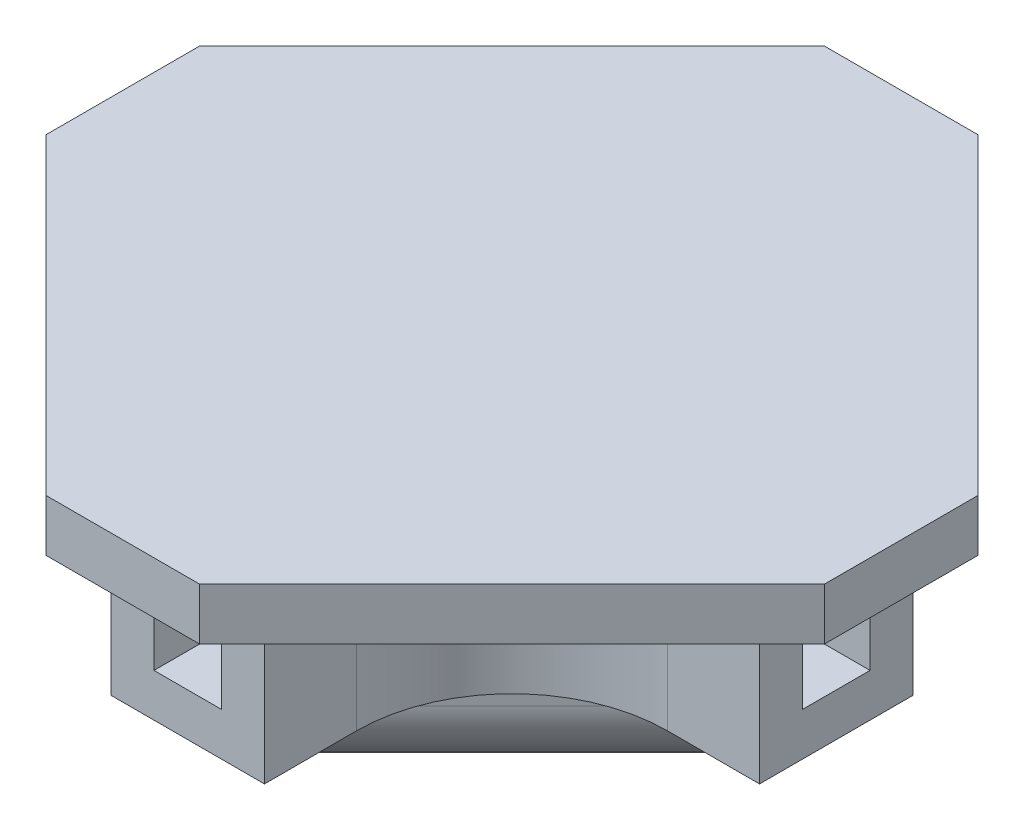
SolidWorks part; units mm, degrees
material "ABS"
ref_plane "Front Plane" through (0, 0, 0) normal (0, 0, 1) x (1, 0, 0)
ref_plane "Top Plane" through (0, 0, 0) normal (0, 1, 0) x (1, 0, 0)
ref_plane "Right Plane" through (0, 0, 0) normal (1, 0, 0) x (0, 0, -1)
sketch "Sketch1" plane through (0, 0, 0) normal (0, 1, 0) x (1, 0, 0)
  line L0 (3.7592, 11.3792) -> (3.7592, 15.875)
  line L1 (-3.7592, -15.875) -> (3.7592, -15.875)
  line L2 (-3.7592, -15.875) -> (-3.7592, -11.3792)
  line L3 (-3.7592, 15.875) -> (3.7592, 15.875)
  line L4 (3.7592, -15.875) -> (3.7592, -11.3792)
  line L5 (-3.7592, -15.875) -> (3.7592, 15.875) construction
  line L6 (-3.7592, 15.875) -> (3.7592, -15.875) construction
  line L7 (-15.875, 3.7592) -> (-11.3792, 3.7592)
  line L8 (-15.875, 3.7592) -> (-15.875, -3.7592)
  line L9 (-15.875, -3.7592) -> (-11.3792, -3.7592)
  line L10 (15.875, 3.7592) -> (15.875, -3.7592)
  line L11 (-15.875, 3.7592) -> (15.875, -3.7592) construction
  line L12 (-15.875, -3.7592) -> (15.875, 3.7592) construction
  line L13 (11.3792, 3.7592) -> (15.875, 3.7592)
  line L14 (-3.7592, 11.3792) -> (-3.7592, 15.875)
  line L15 (11.3792, -3.7592) -> (15.875, -3.7592)
  arc A0 (-3.7592, 11.3792) -> (-11.3792, 3.7592) centre (-11.3792, 11.3792) cw
  arc A1 (-11.3792, -3.7592) -> (-3.7592, -11.3792) centre (-11.3792, -11.3792) cw
  arc A2 (3.7592, -11.3792) -> (11.3792, -3.7592) centre (11.3792, -11.3792) cw
  arc A3 (11.3792, 3.7592) -> (3.7592, 11.3792) centre (11.3792, 11.3792) cw
  point P0 (0, 0)
  point P6 (0, 0)
  point P17 (-3.7592, 3.7592)
  point P22 (3.7592, -3.7592)
  point P25 (3.7592, 3.7592)
  dimension "D5" = 7.62
  dimension "D1" = 7.5184
  dimension "D2" = 7.5184
  dimension "D3" = 31.75
  dimension "D4" = 31.75
extrude "Boss-Extrude1" add sketch "Sketch1" against normal blind 7.5184
sketch "Sketch2" plane through (0, 0, 15.875) normal (0, 0, 1) x (1, 0, 0)
  line L0 (-3.7592, -7.5184) -> (-3.7592, 0) construction
  line L1 (-1.651, -5.4102) -> (1.651, -5.4102)
  line L2 (-1.651, -5.4102) -> (-1.651, -2.1082)
  line L3 (-1.651, -2.1082) -> (1.651, -2.1082)
  line L4 (1.651, -5.4102) -> (1.651, -2.1082)
  line L5 (-1.651, -5.4102) -> (1.651, -2.1082) construction
  line L6 (-1.651, -2.1082) -> (1.651, -5.4102) construction
  point P0 (0, -3.7592)
  dimension "D1" = 3.302
  dimension "D2" = 3.302
  dimension "D3" = 3.7592
  dimension "D4" = 3.7592
extrude "Cut-Extrude1" cut sketch "Sketch2" against normal blind 12.7
ref_point "Point1"
ref_axis "Axis1" through (0, -22.3909, 0) along (0, 1, 0)
pattern_circular "CirPattern1" count 4 over 360 about axis through (0, -22.3909, 0) along (0, 1, 0) of "Cut-Extrude1"
sketch "Sketch4" plane through (0, 0, 0) normal (0, 1, 0) x (1, 0, 0)
  line L0 (3.7592, 19.05) -> (19.05, 3.7592)
  line L2 (-19.05, -3.7592) -> (-19.05, 3.7592)
  line L4 (19.05, -3.7592) -> (19.05, 3.7592)
  line L7 (-3.7592, -19.05) -> (3.7592, -19.05)
  line L9 (-3.7592, 19.05) -> (3.7592, 19.05)
  line L13 (19.05, -3.7592) -> (3.7592, -19.05)
  line L14 (-3.7592, -19.05) -> (-19.05, -3.7592)
  line L15 (-19.05, 3.7592) -> (-3.7592, 19.05)
  dimension "D1" = 38.1
  dimension "D2" = 38.1
extrude "Boss-Extrude2" add sketch "Sketch4" along normal blind 2.54
ref_plane "Plane1" through (0, 0, 0) normal (-0.7071, 0, 0.7071) x (0.7071, 0, 0.7071)
ref_plane "Plane2" through (0, -7.5184, 0) normal (0, -1, 0) x (-1, 0, 0)
sketch "Sketch6" plane through (0, 0, 0) normal (-0.7071, 0, 0.7071) x (0.7071, 0, 0.7071)
  line L3 (-17.4625, -7.5184) -> (17.4625, -7.5184) construction
  line L4 (-3.81, -11.3284) -> (-3.81, -7.5184)
  line L5 (3.81, -11.3284) -> (3.81, -7.5184)
  line L6 (-3.81, -7.5184) -> (3.81, -7.5184)
  line L7 (0, -22.3909) -> (0, 14.8174) construction
  circle A0 centre (0, -11.3284) radius 2.2225
  circle A1 centre (0, -11.3284) radius 3.81 construction
  arc A2 (-3.81, -11.3284) -> (3.81, -11.3284) centre (0, -11.3284) ccw
  point P0 (0, -7.5184)
  dimension "D2" = 7.62
  dimension "D3" = 4.445
extrude "Boss-Extrude3" add sketch "Sketch6" along normal up to surface and the other way up to surface up to face at (-6.7801, -3.7592, 6.7801) other way up to face at (6.7801, -3.7592, -6.7801)
